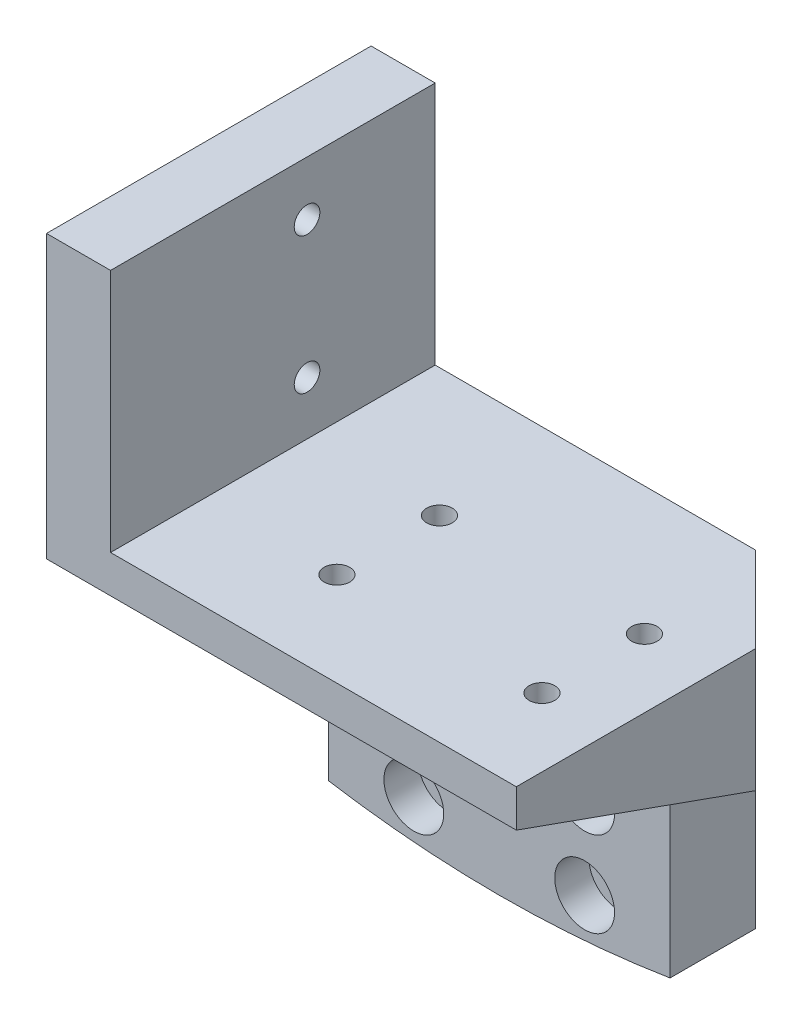
SolidWorks part; units mm, degrees
ref_plane "Plan de face" through (0, 0, 0) normal (0, 0, 1) x (1, 0, 0)
ref_plane "Plan de dessus" through (0, 0, 0) normal (0, 1, 0) x (1, 0, 0)
ref_plane "Plan de droite" through (0, 0, 0) normal (1, 0, 0) x (0, 0, -1)
sketch "Esquisse1" plane through (0, 0, 0) normal (0, 0, 1) x (1, 0, 0)
  line L0 (-20, -123.3896) -> (-20, -99.4)
  line L1 (-20, -99.4) -> (20, -99.4)
  line L2 (20, -99.4) -> (20, -123.3896)
  arc A0 (20, -123.3896) -> (-20, -123.3896) centre (0, 0) cw
  point P4 (0, -125)
  dimension "D1" = 125
  dimension "D3" = 25.6
  dimension "D2" = 40
extrude "Boss.-Extru.1" add sketch "Esquisse1" along normal blind 10
sketch "Esquisse2" plane through (0, 0, 10) normal (0, 0, 1) x (1, 0, 0)
  line L0 (0, -99.4) -> (0, -125) construction
  line L1 (20, -99.4) -> (-20, -99.4) construction
  line L2 (-10, -110) -> (-10, -120) construction
  line L3 (-10, -120) -> (10, -120) construction
  arc A0 (-20, -123.3896) -> (20, -123.3896) centre (0, 0) ccw construction
  circle A1 centre (-10, -110) radius 1.75
  circle A2 centre (-10, -120) radius 1.75
  circle A3 centre (10, -110) radius 1.75
  circle A4 centre (10, -120) radius 1.75
  point P16 (0, -112.2)
  point P17 (0, -120)
  point P18 (-10, -118.85)
  point P19 (-10, -119.333)
  dimension "D3" = 3.5
  dimension "D1" = 10
  dimension "D2" = 20
  dimension "D4" = 120
extrude "Enlèv. mat.-Extru.1" cut sketch "Esquisse2" against normal up to next
sketch "Esquisse4" plane through (0, 0, 10) normal (0, 0, 1) x (1, 0, 0)
  circle A0 centre (-10, -110) radius 3.5
  circle A1 centre (10, -110) radius 3.5
  circle A2 centre (10, -120) radius 3.5
  circle A3 centre (-10, -120) radius 3.5
  dimension "D1" = 7
extrude "Enlèv. mat.-Extru.2" cut sketch "Esquisse4" against normal blind 4
sketch "Esquisse5" plane through (0, -99.4, 0) normal (0, 1, 0) x (1, 0, 0)
  line L1 (-20, 0) -> (30, 0)
  line L2 (-20, 0) -> (-20, -38)
  line L3 (-20, -38) -> (30, -38)
  line L4 (30, 0) -> (30, -38)
  dimension "D1" = 50
  dimension "D2" = 38
extrude "Boss.-Extru.2" add sketch "Esquisse5" along normal blind 14.4
sketch "Esquisse6" plane through (0, -99.4, 0) normal (0, -1, 0) x (1, 0, 0)
  line L0 (20, 10) -> (-20, 10) construction
  line L1 (30, 38) -> (30, 0) construction
  circle A0 centre (-2, 27) radius 1.5
  circle A1 centre (22, 27) radius 1.5
  circle A2 centre (-2, 15) radius 1.5
  circle A3 centre (22, 15) radius 1.5
  dimension "D1" = 3
  dimension "D2" = 5
  dimension "D3" = 24
  dimension "D4" = 12
  dimension "D5" = 8
extrude "Enlèv. mat.-Extru.3" cut sketch "Esquisse6" against normal up to next
sketch "Esquisse7" plane through (0, -99.4, 0) normal (0, -1, 0) x (1, 0, 0)
  circle A0 centre (-2, 27) radius 3
  circle A1 centre (22, 27) radius 3
  circle A2 centre (22, 15) radius 3
  circle A3 centre (-2, 15) radius 3
  dimension "D1" = 6
extrude "Enlèv. mat.-Extru.4" cut sketch "Esquisse7" against normal offset from surface (9.4 mm away) 5 up to face at (22, -85, 28.5)
chamfer "Chanfrein1" distance 10 angle 45 1 edges at (30, -92.2, 0)
chamfer "Chanfrein2" distance 28 distance2 10 1 edges at (5, -99.4, 38) first distance on face at (-2, -99.4, 12)
sketch "Esquisse8" plane through (-20, 0, 0) normal (-1, 0, 0) x (0, 0, 1)
  line L0 (10, -99.4) -> (0, -99.4)
  line L1 (0, -85) -> (0, -123.3896) construction
  line L2 (0, -99.4) -> (0, -56.4)
  line L3 (0, -56.4) -> (38, -56.4)
  line L4 (38, -56.4) -> (38, -89.4)
  line L5 (38, -89.4) -> (10, -99.4)
  dimension "D1" = 43
extrude "Boss.-Extru.3" add sketch "Esquisse8" along normal blind 5
sketch "Esquisse9" plane through (-20, 0, 0) normal (1, 0, 0) x (0, 0, -1)
  line L4 (-38, -85) -> (0, -85)
  line L5 (0, -85) -> (0, -56.4)
  line L6 (0, -56.4) -> (-38, -56.4)
  line L7 (-38, -56.4) -> (-38, -85)
  line L8 (-38, -85) -> (0, -85)
  line L9 (0, -85) -> (0, -56.4)
  line L10 (0, -56.4) -> (-38, -56.4)
  line L11 (-38, -56.4) -> (-38, -85)
  dimension "D1" = 0
extrude "Boss.-Extru.4" add sketch "Esquisse9" along normal blind 2.5
chamfer "Chanfrein3" distance 5 angle 45 1 edges at (-20, -99.4, 5)
sketch "Esquisse10" plane through (-25, 0, 0) normal (-1, 0, 0) x (0, 0, 1)
  line L0 (38, -56.4) -> (0, -56.4) construction
  line L2 (13.5, -90) -> (16.5, -90) construction
  line L3 (13.5, -90) -> (16.5, -90) construction
  circle A0 centre (15, -62.75) radius 1.5
  circle A1 centre (15, -78.75) radius 1.5
  point P7 (15, -90)
  dimension "D1" = 3
  dimension "D2" = 16
  dimension "D3" = 6.35
extrude "Enlèv. mat.-Extru.5" cut sketch "Esquisse10" against normal up to next
sketch "Esquisse11" plane through (-25, 0, 0) normal (-1, 0, 0) x (0, 0, 1)
  circle A0 centre (15, -62.75) radius 3
  circle A1 centre (15, -78.75) radius 3
  dimension "D1" = 6
extrude "Enlèv. mat.-Extru.6" cut sketch "Esquisse11" against normal offset from surface (2.5 mm away) 5 up to face at (-17.5, -61.25, 15)
